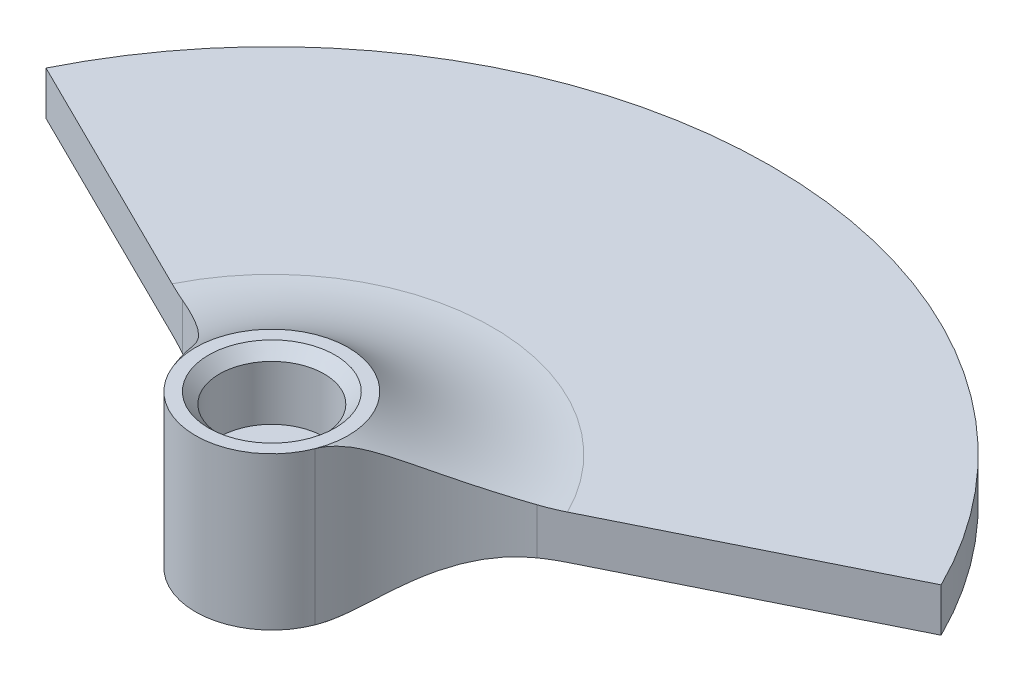
SolidWorks part; units mm, degrees
ref_plane "Front Plane" through (0, 0, 0) normal (0, 0, 1) x (1, 0, 0)
ref_plane "Top Plane" through (0, 0, 0) normal (0, 1, 0) x (1, 0, 0)
ref_plane "Right Plane" through (0, 0, 0) normal (1, 0, 0) x (0, 0, -1)
sketch "Sketch1" plane through (0, 0, 0) normal (0, 1, 0) x (1, 0, 0)
  circle A0 centre (0, 0) radius 2.5
  circle A1 centre (0, 0) radius 3.5
  dimension "D1" = 5
  dimension "D2" = 1
extrude "Boss-Extrude1" add sketch "Sketch1" along normal blind 3
sketch "Sketch2" plane through (0, 3, 0) normal (0, 1, 0) x (1, 0, 0)
  circle A0 centre (0, 0) radius 3.5
extrude "Boss-Extrude2" add sketch "Sketch2" along normal blind 1
sketch "Sketch3" plane through (0, 4, 0) normal (0, 1, 0) x (1, 0, 0)
  circle A0 centre (0, 0) radius 1.3
  dimension "D1" = 2.6
extrude "Cut-Extrude1" cut sketch "Sketch3" against normal up to next
sketch "Sketch4" plane through (0, 4, 0) normal (0, 1, 0) x (1, 0, 0)
  circle A0 centre (0, 0) radius 2.4
  circle A1 centre (0, 0) radius 3.5
  dimension "D1" = 4.8
extrude "Boss-Extrude3" add sketch "Sketch4" along normal blind 3
chamfer "Chamfer1" distance 0.5 angle 45 2 edges at (0, 7, 2.4) (0, 0, 2.5)
ref_plane "Plane1" through (0, 3.5, 0) normal (0, 1, 0) x (1, 0, 0)
sketch "Sketch5" plane through (0, 3.5, 0) normal (0, 1, 0) x (1, 0, 0)
  line L0 (0, 0) -> (15.4603, 0) construction
  arc A0 (-0.0885, -3.4989) -> (21.9115, -1) centre (1.9409, 76.7271) ccw
  circle A1 centre (0, 0) radius 3.5 construction
  arc A3 (-0.0885, 3.4989) -> (21.9115, 1) centre (1.9409, -76.7271) cw
  arc A4 (21.9115, 1) -> (21.9115, -1) centre (21.6546, 0) cw
  arc A5 (-0.0885, -3.4989) -> (-0.0885, 3.4989) centre (0, 0) ccw
  dimension "D1" = 22
  dimension "D2" = 1
extrude "Boss-Extrude4" [suppressed] add sketch "Sketch5" along normal blind 1 and the other way blind 1
sketch "Sketch6" plane through (0, 3.5, 0) normal (0, 1, 0) x (1, 0, 0)
  line L0 (-20.5197, 10.1662) -> (-3.1362, 1.5538)
  line L1 (20.5197, 10.1662) -> (3.1362, 1.5538)
  line L2 (0, 0) -> (0, -4.7859) construction
  arc A0 (-20.5197, 10.1662) -> (20.5197, 10.1662) centre (0, 0) cw
  circle A1 centre (0, 0) radius 2.9 construction
  circle A2 centre (0, 0) radius 3.5 construction
  arc A3 (-3.1362, 1.5538) -> (3.1362, 1.5538) centre (0, 0) cw
  dimension "D1" = 20
extrude "Boss-Extrude5" add sketch "Sketch6" along normal blind 1 and the other way blind 1
fillet "Fillet1" radius 10 4 edges at (0, 4.5, -3.5) (0, 2.5, -3.5) (3.1362, 3.5, -1.5538) (-3.1362, 3.5, -1.5538)
